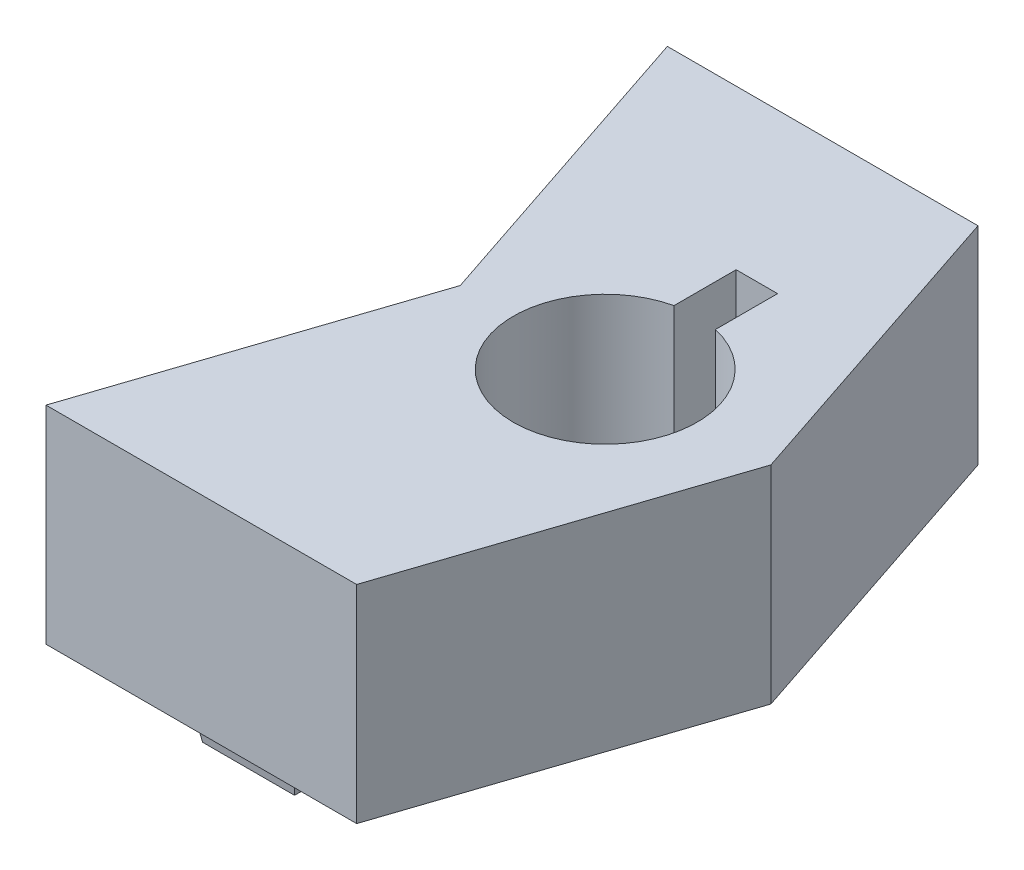
SolidWorks part; units mm, degrees
ref_plane "Front Plane" through (0, 0, 0) normal (0, 0, 1) x (1, 0, 0)
ref_plane "Top Plane" through (0, 0, 0) normal (0, 1, 0) x (1, 0, 0)
ref_plane "Right Plane" through (0, 0, 0) normal (1, 0, 0) x (0, 0, -1)
sketch "Sketch1" plane through (0, 0, 0) normal (0, 1, 0) x (1, 0, 0)
  line L0 (0, 0) -> (19.05, 0)
  line L1 (19.05, 0) -> (25.4, 19.05)
  line L2 (25.4, 19.05) -> (19.05, 38.1)
  line L3 (19.05, 38.1) -> (0, 38.1)
  line L4 (0, 38.1) -> (6.35, 19.05)
  line L5 (6.35, 19.05) -> (0, 0)
  dimension "D1" = 19.05
  dimension "D2" = 38.1
  dimension "D3" = 6.35
  dimension "D5" = 19.05
extrude "Boss-Extrude1" add sketch "Sketch1" along normal blind 12.7
sketch "Sketch2" plane through (0, 12.7, 0) normal (0, -1, 0) x (1, 0, 0)
  line L0 (25.4, -19.05) -> (6.35, -19.05) construction
  line L1 (6.35, -19.05) -> (0, 0) construction
  circle A0 centre (15.24, -19.05) radius 5.635
  dimension "D1" = 11.27
  dimension "D2" = 8.89
extrude "Haptic Motor Cutout" cut sketch "Sketch2" along normal blind 9.558 contours A0
sketch "Sketch3" plane through (0, 0, 0) normal (0, -1, 0) x (1, 0, 0)
  line L8 (16.51, -24.54) -> (13.97, -24.54)
  line L9 (16.51, -24.54) -> (16.51, -28.35)
  line L10 (13.97, -24.54) -> (13.97, -28.35)
  line L11 (16.51, -28.35) -> (13.97, -28.35)
  circle A3 centre (15.24, -19.05) radius 5.635 construction
  dimension "D1" = 2.54
  dimension "D2" = 3.81
extrude "Haptic Wire Cutout" cut sketch "Sketch3" against normal through all
ref_plane "MidPlane" through (0, 0, -19.05) normal (0, 0, -1) x (-1, 0, 0)
sketch "Sketch4" plane through (0, 0, 0) normal (0, -1, 0) x (1, 0, 0)
  line L0 (19.05, -38.1) -> (0, -38.1) construction
  line L1 (13.97, -36.83) -> (7.62, -36.83)
  line L2 (13.97, -36.83) -> (13.97, -34.29)
  line L3 (13.97, -34.29) -> (7.62, -34.29)
  line L4 (7.62, -36.83) -> (7.62, -34.29)
  line L5 (0, -6.985) -> (0, 6.985) construction
  dimension "D1" = 2.54
  dimension "D2" = 6.35
  dimension "D3" = 1.27
  dimension "D4" = 7.62
extrude "Pins" add sketch "Sketch4" along normal blind 2.032 draft 10
mirror "Mirror1" about plane through (0, 0, -19.05) normal (0, 0, -1) of "Pins"
ref_point "Point1"
ref_axis "Axis1" through (0, 12.7, -38.1) along (0, 0, 1)
sketch "Sketch5" plane through (0, 12.7, 0) normal (0, 1, 0) x (1, 0, 0)
  line L0 (0, 38.1) -> (0, 0) construction
  line L1 (0, 19.05) -> (25.4, 19.05) construction
equation "\"Arrow Height\"= 1.5in"
equation "\"Button Height\"= 2in"
equation "\"Button Width\"= 4in"
equation "\"Haptic Diameter\"= 10mm"
equation "\"Haptic Thickness\"= 2.7mm"
equation "\"D2@Sketch1\"=\"Arrow Height\""
equation "\"D5@Sketch1\"=\"Arrow Height\"/2"
equation "\"D1@Sketch2\"=\"Haptic Diameter\"+.05in"
equation "\"D1@Haptic Motor Cutout\"=\"Haptic Thickness\" + .02+.25"
equation "\"D1\" = \"Haptic Thickness\" + .02 + .25"
equation "\"Arrow Spacing\"= 1in"
equation "\"Arrow Width\"= 01in"
equation "\"Haptic Wire Angle\"= 63.43"
equation "\"Haptic Wire Width\"= .1in"
equation "\"Haptic Wire Height\"= .15in"
